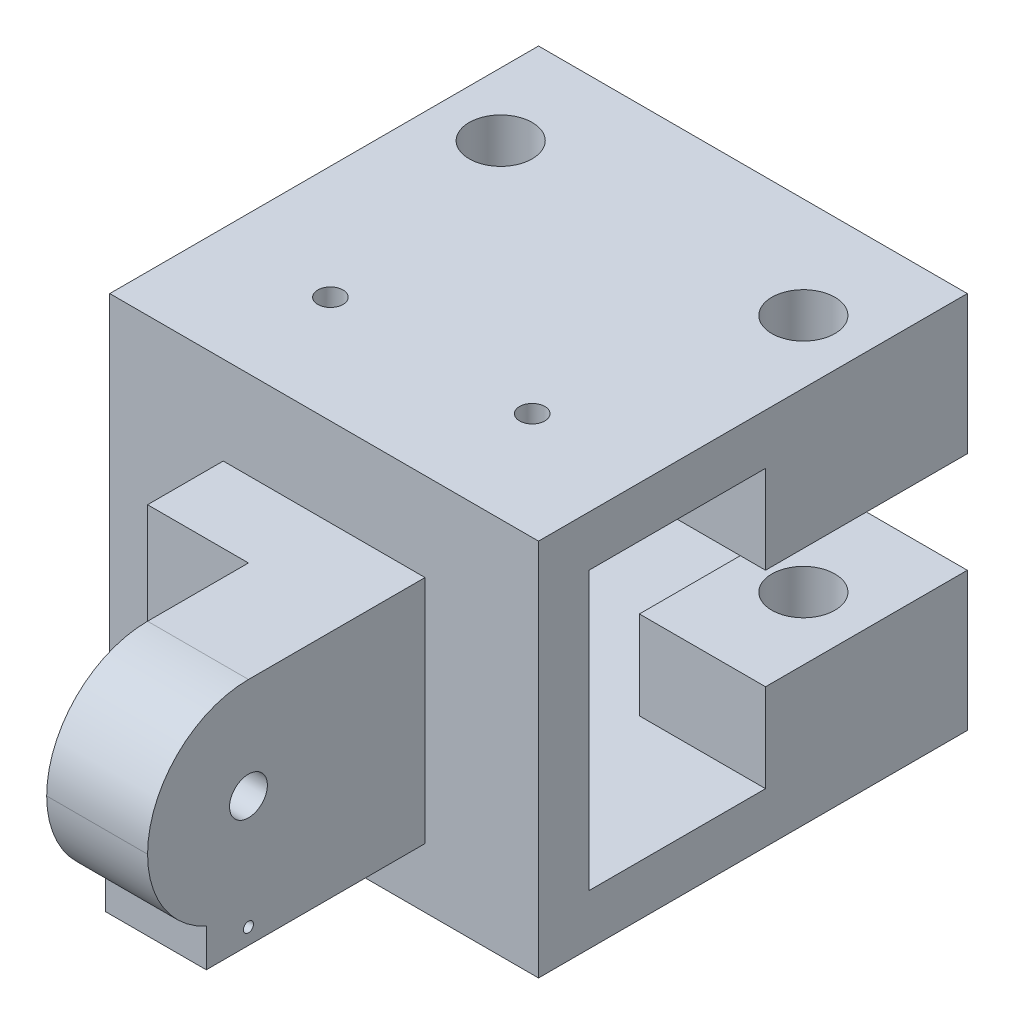
SolidWorks part; units mm, degrees
ref_plane "前视基准面" through (0, 0, 0) normal (0, 0, 1) x (1, 0, 0)
ref_plane "上视基准面" through (0, 0, 0) normal (0, 1, 0) x (1, 0, 0)
ref_plane "右视基准面" through (0, 0, 0) normal (1, 0, 0) x (0, 0, -1)
sketch "草图1" plane through (0, 0, 0) normal (0, 0, 1) x (1, 0, 0)
  line L0 (40, 0) -> (40, -80) construction
  line L1 (0, 0) -> (80, 0)
  line L2 (0, 0) -> (0, -80)
  line L3 (0, -80) -> (80, -80)
  line L4 (80, 0) -> (80, -80)
  line L5 (55, 0) -> (55, -80) construction
  line L6 (25, 0) -> (25, -80) construction
  line L8 (25, -80) -> (55, -80)
  line L9 (25, -80) -> (25, 0)
  line L10 (25, 0) -> (55, 0)
  line L11 (55, -80) -> (55, 0)
  dimension "D1" = 80
  dimension "D2" = 15
  dimension "D3" = 15
extrude "凸台-拉伸1" add sketch "草图1" along normal blind 30 contours L3 L9 L1 L2 | L3 L11 L1 L9 | L11 L3 L4 L1 region at (12.5, -40, 0) region at (40, -40, 0) region at (67.5, -40, 0)
sketch "草图2" plane through (0, 0, 30) normal (0, 0, 1) x (1, 0, 0)
  line L0 (0, 0) -> (80, 0) construction
  line L1 (40, 0) -> (80, 0)
  line L2 (40, 0) -> (40, -80)
  line L3 (40, -80) -> (80, -80)
  line L4 (80, 0) -> (80, -80)
  line L5 (0, -80) -> (80, -80) construction
  line L6 (80, 0) -> (80, -80) construction
  line L7 (0, 0) -> (0, -80) construction
  dimension "D1" = 0
  dimension "D2" = 40
extrude "凸台-拉伸2" add sketch "草图2" along normal blind 80 contours L2 L1 L4 L3
fillet "圆角1" radius 40 2 edges at (60, 0, 110) (60, -80, 110)
sketch "草图3" plane through (40, 0, 0) normal (-1, 0, 0) x (0, 0, 1)
  line L3 (70, 0) -> (30, 0)
  line L4 (30, 0) -> (30, -80)
  line L5 (30, -80) -> (70, -80)
  line L6 (70, 0) -> (30, 0)
  line L7 (30, 0) -> (30, -80)
  line L8 (30, -80) -> (70, -80)
  circle A0 centre (70, -40) radius 7.5
  arc A2 (70, -80) -> (110, -40) centre (70, -40) ccw
  arc A3 (110, -40) -> (70, 0) centre (70, -40) ccw
  arc A4 (70, -80) -> (110, -40) centre (70, -40) ccw
  arc A5 (110, -40) -> (70, 0) centre (70, -40) ccw
  dimension "D2" = 15
  dimension "D1" = 0
extrude "切除-拉伸1" cut sketch "草图3" against normal through all contours A0
sketch "草图6" plane through (0, 0, 0) normal (0, 0, -1) x (-1, 0, 0)
  line L1 (-125, 35) -> (45, 35)
  line L2 (-125, 35) -> (-125, -115)
  line L3 (-125, -115) -> (45, -115)
  line L4 (45, 35) -> (45, -115)
  line L5 (0, -80) -> (-80, -80) construction
  line L6 (0, 0) -> (0, -80) construction
  line L7 (0, 0) -> (-80, 0) construction
  line L9 (0, -80) -> (-80, -80)
  line L10 (0, 0) -> (0, -80)
  line L11 (0, 0) -> (-80, 0)
  line L12 (-80, 0) -> (-80, -80)
  point P4 (-40, 35)
  point P5 (-40, 0)
  point P9 (-80, -40)
  point P11 (-125, -40)
  dimension "D1" = 170
  dimension "D2" = 150
extrude "凸台-拉伸5" add sketch "草图6" along normal blind 20 separate body contours L2 L1 L4 L3
sketch "草图7" plane through (0, 0, -20) normal (0, 0, -1) x (-1, 0, 0)
  line L1 (-125, 35) -> (45, 35)
  line L2 (-125, 35) -> (-125, 15)
  line L3 (-125, 15) -> (45, 15)
  line L4 (-125, -115) -> (45, -115)
  line L5 (45, -115) -> (45, 35)
  line L6 (45, 35) -> (-125, 35)
  line L7 (-125, 35) -> (-125, -115)
  line L8 (-125, -115) -> (45, -115)
  line L9 (45, -115) -> (45, 35)
  line L10 (45, 35) -> (-125, 35)
  line L11 (-125, 35) -> (-125, -115)
  line L12 (45, 35) -> (45, 15)
  line L13 (-125, -115) -> (45, -115)
  line L14 (-125, -115) -> (-125, -95)
  line L15 (-125, -95) -> (45, -95)
  line L16 (45, -115) -> (45, -95)
  line M7 (-125, -115) -> (45, -115)
  line M8 (45, -115) -> (45, 35)
  line M9 (45, 35) -> (-125, 35)
  line M10 (-125, 35) -> (-125, -115)
  dimension "D2" = 20
  dimension "D3" = 20
  dimension "D1" = 0
extrude "凸台-拉伸6" add sketch "草图7" along normal blind 150 contours L3 M10 M8 M9 | L15 L11 M7 M8 region at (40, 25, -20) region at (40, -105, -20)
sketch "草图8" plane through (0, 35, 0) normal (0, 1, 0) x (1, 0, 0)
  line L1 (-22.8537, 50) -> (218.3867, 50) construction
  line L3 (125, 95) -> (-45, 95) construction
  line L4 (-45, 0) -> (125, 0)
  line L5 (125, 0) -> (125, 170)
  line L6 (125, 170) -> (-45, 170)
  line L7 (-45, 170) -> (-45, 0)
  line L8 (-45, 0) -> (125, 0)
  line L9 (125, 0) -> (125, 170)
  line L10 (125, 170) -> (-45, 170)
  line L11 (-45, 170) -> (-45, 0)
  circle A0 centre (75, 50) radius 5
  circle A1 centre (5, 50) radius 5
  circle A2 centre (15, 145) radius 2
  circle A3 centre (65, 95) radius 2
  dimension "D5" = 10
  dimension "D7" = 4
  dimension "D11" = 25
  dimension "D2" = 50
  dimension "D3" = 60
  dimension "D4" = 60
  dimension "D6" = 45
  dimension "D8" = 50
  dimension "D9" = 50
  dimension "D10" = 50
  dimension "D1" = 0
sketch "草图9" plane through (80, 0, 0) normal (1, 0, 0) x (0, 0, -1)
  line L0 (-70, -40) -> (-70, -85) construction
  line L1 (-86.7216, -76.3371) -> (-86.7216, -91.3371)
  line L2 (-86.7216, -91.3371) -> (0, -91.3371)
  line L3 (0, 0) -> (-70, 0)
  line L4 (-70, -80) -> (0, -80)
  line L5 (0, -80) -> (0, 0)
  line L7 (-70, -80) -> (0, -80)
  line L9 (0, -91.3371) -> (0, -80)
  line L10 (0, -80) -> (0, -91.3371)
  arc A2 (-70, 0) -> (-110, -40) centre (-70, -40) ccw
  arc A3 (-110, -40) -> (-70, -80) centre (-70, -40) ccw
  arc A5 (-86.7216, -76.3371) -> (-70, -80) centre (-70, -40) ccw
  arc M12 (-110, -40) -> (-70, -80) centre (-70, -40) ccw
  line M13 (-70, -80) -> (0, -80)
  dimension "D2" = 45
  dimension "D3" = 15
  dimension "D4" = 86.7216
  dimension "D1" = 0
extrude "凸台-拉伸7" add sketch "草图9" against normal up to surface (40 mm away) contours L2 L9 L1 M13 M12 region at (80, -85.5337, 44.1437) up to face at (40, -47.5, 70)
sketch "草图10" plane through (80, 0, 0) normal (1, 0, 0) x (0, 0, -1)
  line L0 (-70, -40) -> (-70, -85) construction
  circle A1 centre (-70, -85) radius 2
  dimension "D2" = 4
  dimension "D1" = 45
extrude "切除-拉伸3" cut sketch "草图10" against normal through all
sketch "草图11" plane through (0, -95, 0) normal (0, 1, 0) x (1, 0, 0)
  line L0 (40, 170) -> (40, 34.263) construction
  line L1 (-45, 90) -> (5, 90)
  line L2 (125, 170) -> (75, 170)
  line L3 (125, 170) -> (125, 90)
  line L4 (-45, 20) -> (125, 20)
  line L5 (125, 20) -> (125, 170)
  line L6 (125, 170) -> (-45, 170)
  line L7 (-45, 170) -> (-45, 20)
  line L8 (-45, 20) -> (125, 20) construction
  line L9 (125, 20) -> (125, 170) construction
  line L10 (125, 170) -> (-45, 170) construction
  line L11 (-45, 170) -> (-45, 20) construction
  line L12 (125, 90) -> (75, 90)
  line L13 (75, 170) -> (75, 90)
  line L14 (5, 170) -> (5, 90)
  line L15 (-45, 170) -> (5, 170)
  line L16 (-45, 170) -> (-45, 90)
  dimension "D2" = 80
  dimension "D3" = 50
  dimension "D1" = 0
extrude "凸台-拉伸8" add sketch "草图11" along normal up to surface (110 mm away) contours L1 L14 L15 L16 | L3 L2 L13 L12 up to face at (40, 15, -95)
sketch "草图12" plane through (125, 0, 0) normal (1, 0, 0) x (0, 0, -1)
  line L0 (170, -40) -> (90, -40) construction
  line L1 (90, 15) -> (90, -95) construction
  line L3 (90, -60) -> (170, -60)
  line L4 (0, 35) -> (0, -115)
  line L5 (0, -115) -> (170, -115)
  line L6 (170, -115) -> (170, 35)
  line L7 (170, 35) -> (0, 35)
  line L8 (0, 35) -> (0, -115) construction
  line L9 (0, -115) -> (170, -115) construction
  line L10 (170, -115) -> (170, 35) construction
  line L11 (170, 35) -> (0, 35) construction
  line L12 (90, -60) -> (90, -20)
  line L13 (90, -20) -> (170, -20)
  line L14 (170, -60) -> (170, -20)
  line L15 (90, -60) -> (170, -20) construction
  line L16 (90, -20) -> (170, -60) construction
  point P8 (130, -40)
  dimension "D2" = 40
  dimension "D1" = 0
extrude "切除-拉伸4" cut sketch "草图12" against normal through all
sketch "草图13" plane through (0, 35, 0) normal (0, 1, 0) x (1, 0, 0)
  line L0 (125, 130) -> (-62.9737, 130) construction
  line L1 (100, 170) -> (100, 78.8659) construction
  line L2 (-20, 170) -> (-20, 130) construction
  line L4 (5, 90) -> (5, 170)
  line L5 (5, 170) -> (-45, 170)
  line L6 (-45, 170) -> (-45, 90)
  line L7 (-45, 90) -> (5, 90)
  line L8 (5, 90) -> (5, 170)
  line L9 (5, 170) -> (-45, 170)
  line L10 (-45, 170) -> (-45, 90)
  line L11 (-45, 90) -> (5, 90)
  line L12 (75, 90) -> (125, 90)
  line L13 (125, 90) -> (125, 170)
  line L14 (125, 170) -> (75, 170)
  line L15 (75, 170) -> (75, 90)
  line L16 (75, 90) -> (125, 90)
  line L17 (125, 90) -> (125, 170)
  line L18 (125, 170) -> (75, 170)
  line L19 (75, 170) -> (75, 90)
  circle A0 centre (100, 130) radius 12.5
  circle A1 centre (-20, 130) radius 12.5
  dimension "D3" = 25
  dimension "D4" = 25
  dimension "D1" = 0
  dimension "D2" = 0
extrude "切除-拉伸5" cut sketch "草图13" against normal through all contours A1 | A0
sketch "草图14" plane through (0, -115, 0) normal (0, -1, 0) x (1, 0, 0)
  line L0 (40, 0) -> (40, -85) construction
  line L1 (40, -42.5) -> (0, -42.5) construction
  line L4 (125, 0) -> (-45, 0)
  line L5 (-45, 0) -> (-45, -170)
  line L6 (-45, -170) -> (125, -170)
  line L7 (125, -170) -> (125, 0)
  line L8 (125, 0) -> (-45, 0) construction
  line L9 (-45, 0) -> (-45, -170) construction
  line L10 (-45, -170) -> (125, -170) construction
  line L11 (125, -170) -> (125, 0) construction
  circle A0 centre (0, -42.5) radius 5
  circle A1 centre (80, -42.5) radius 5
  dimension "D3" = 10
  dimension "D2" = 40
  dimension "D1" = 0
extrude "切除-拉伸6" cut sketch "草图14" against normal through all
sketch "草图15" plane through (0, 0, -20) normal (0, 0, -1) x (-1, 0, 0)
  line L0 (-125, -95) -> (45, -95) construction
  line L1 (45, 15) -> (23.2471, 15)
  line L2 (45, 15) -> (45, -95)
  line L3 (45, -95) -> (23.2471, -95)
  line L4 (23.2471, 15) -> (23.2471, -95)
extrude "凸台-拉伸9" add sketch "草图15" along normal blind 50
sketch "草图16" plane through (-45, 0, 0) normal (-1, 0, 0) x (0, 0, 1)
  line L0 (0, -115) -> (-20, -115) construction
  line L1 (-170, -115) -> (0, -115) construction
  line L2 (-20, -115) -> (-40, -115) construction
  line L3 (-20, -115) -> (-20, -80) construction
  line L4 (-40, -115) -> (-40, -80) construction
  circle A0 centre (-20, -80) radius 2
  circle A1 centre (-40, -80) radius 2
  dimension "D5" = 4
  dimension "D1" = 20
  dimension "D2" = 20
  dimension "D3" = 35
  dimension "D4" = 35
extrude "切除-拉伸7" cut sketch "草图16" against normal up to surface (21.7529 mm away) up to face at (-23.2471, -40, -45)
sketch "草图17" plane through (0, -115, 0) normal (0, -1, 0) x (1, 0, 0)
  line L0 (-25, 0) -> (-25, -110) construction
  line L1 (125, 0) -> (-45, 0) construction
  line L2 (-25, -110) -> (25, -110) construction
  line L4 (-45, -170) -> (-45, 0) construction
  line L5 (25, 0) -> (25, -110) construction
  circle A0 centre (-25, -110) radius 2
  circle A1 centre (25, -110) radius 2
  point P4 (25, -95.3365)
  dimension "D4" = 4
  dimension "D1" = 110
  dimension "D2" = 20
  dimension "D3" = 50
extrude "切除-拉伸8" cut sketch "草图17" against normal up to surface (20 mm away) up to face at (0, -95, -37.5)
